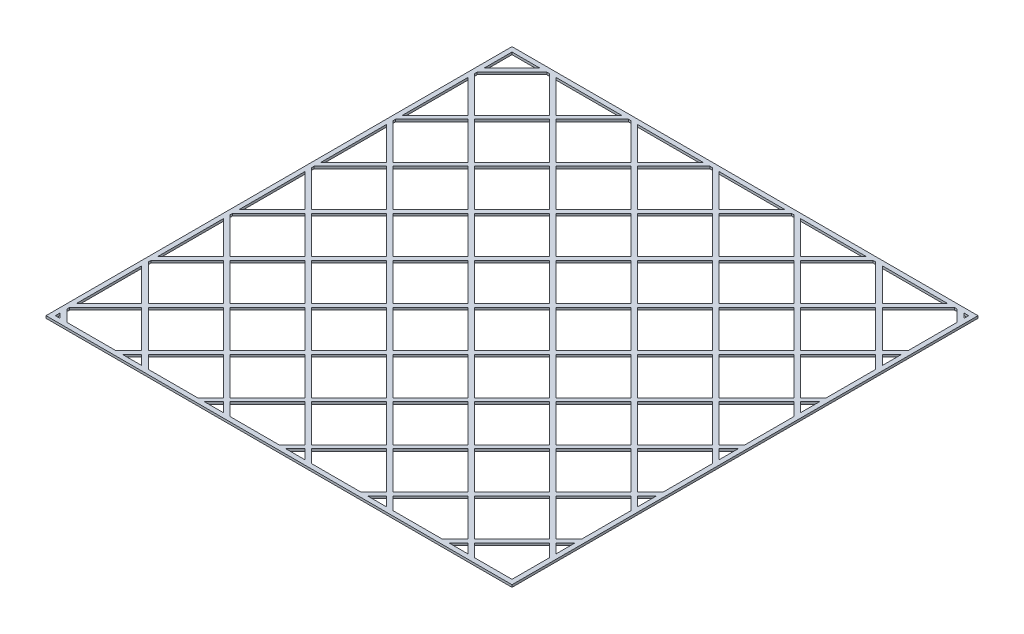
SolidWorks part; units mm, degrees
material "6061 Alloy"
ref_plane "Front Plane" through (0, 0, 0) normal (0, 0, 1) x (1, 0, 0)
ref_plane "Top Plane" through (0, 0, 0) normal (0, 1, 0) x (1, 0, 0)
ref_plane "Right Plane" through (0, 0, 0) normal (1, 0, 0) x (0, 0, -1)
sketch "Sketch1" plane through (0, 0, 0) normal (0, 1, 0) x (1, 0, 0)
  line L1 (-500, -500) -> (500, -500)
  line L2 (-500, -500) -> (-500, 500)
  line L3 (-500, 500) -> (500, 500)
  line L4 (500, -500) -> (500, 500)
  line L5 (-500, -500) -> (500, 500) construction
  line L6 (-500, 500) -> (500, -500) construction
  point P0 (0, 0)
  dimension "D1" = 1000
extrude "Boss-Extrude1" add sketch "Sketch1" along normal mid plane 5
sketch "Sketch2" plane through (0, 2.5, 0) normal (0, 1, 0) x (1, 0, 0)
  line L0 (-412.5, 500) -> (-500, 412.5) construction
  line L1 (-500, 500) -> (-325, 500)
  line L2 (-500, 500) -> (-500, 325)
  line L3 (-500, 325) -> (-325, 325)
  line L4 (-325, 500) -> (-325, 325)
  line L5 (-500, 500) -> (-325, 325) construction
  line L6 (-500, 325) -> (-325, 500) construction
  line L7 (-500, 412.5) -> (-412.5, 325) construction
  line L8 (-412.5, 325) -> (-325, 412.5) construction
  line L9 (-325, 412.5) -> (-412.5, 500) construction
  line L10 (-325, 419.5711) -> (-405.4289, 500)
  line L11 (-419.5711, 500) -> (-500, 419.5711)
  line L12 (-500, 405.4289) -> (-419.5711, 325)
  line L13 (-405.4289, 325) -> (-325, 405.4289)
  line L14 (-332.0711, 412.5) -> (-412.5, 492.9289)
  line L15 (-412.5, 492.9289) -> (-492.9289, 412.5)
  line L16 (-492.9289, 412.5) -> (-412.5, 332.0711)
  line L17 (-412.5, 332.0711) -> (-332.0711, 412.5)
  line L18 (-500, 500) -> (-500, -500) construction
  line L19 (-412.5, 507.0711) -> (-507.0711, 412.5) construction
  line L20 (-507.0711, 412.5) -> (-412.5, 317.9289) construction
  line L21 (-317.9289, 412.5) -> (-412.5, 507.0711) construction
  line L22 (-412.5, 317.9289) -> (-317.9289, 412.5) construction
  line L23 (500, 500) -> (-500, 500) construction
  line L24 (-500, 500) -> (-500, -500)
  line L25 (500, 500) -> (-500, 500)
  point P0 (-412.5, 412.5)
  line M6 (500, 500) -> (-500, 500)
  line M7 (-500, 500) -> (-500, -500)
  dimension "D1" = 175
  dimension "D2" = 5
  dimension "D3" = 5
extrude "Cut-Extrude1" cut sketch "Sketch2" against normal blind 5 contours L11 M6 M7 | L10 L4 M6 | L16 L17 L14 L15 | L13 L3 L4 | L12 L3 M7 region at (-473.1904, 2.5, -473.1904) region at (-351.8096, 2.5, -473.1904) region at (-473.1904, 2.5, -351.8096) region at (-351.8096, 2.5, -351.8096) region at (-412.5, 2.5, -412.5)
pattern_linear "LPattern1" count 6 spacing 175 along (1, 0, 0) count 6 spacing 175 along (0, 0, 1) of "Cut-Extrude1"
sketch "Sketch3" plane through (0, 0, 0) normal (0, 1, 0) x (1, 0, 0)
  line L0 (-490, 490) -> (490, 490)
  line L1 (-500, -500) -> (500, -500)
  line L2 (-500, -500) -> (-500, 500)
  line L3 (-500, 500) -> (500, 500)
  line L4 (500, -500) -> (500, 500)
  line L5 (-500, -500) -> (500, 500) construction
  line L6 (-500, 500) -> (500, -500) construction
  line L7 (490, -490) -> (490, 490)
  line L8 (-490, -490) -> (490, -490)
  line L9 (-490, -490) -> (-490, 490)
  point P0 (0, 0)
  dimension "D1" = 1000
  dimension "D2" = 10
extrude "Boss-Extrude2" add sketch "Sketch3" along normal mid plane 5
equation "\"Dim1Shape\"=175"
equation "\"D1@Sketch2\"=\"Dim1Shape\""
equation "\"D3@LPattern1\"=\"Dim1Shape\""
equation "\"D4@LPattern1\"=\"Dim1Shape\""
equation "\"D1@LPattern1\"=1000/\"Dim1Shape\""
equation "\"D2@LPattern1\"=1000/\"Dim1Shape\""
